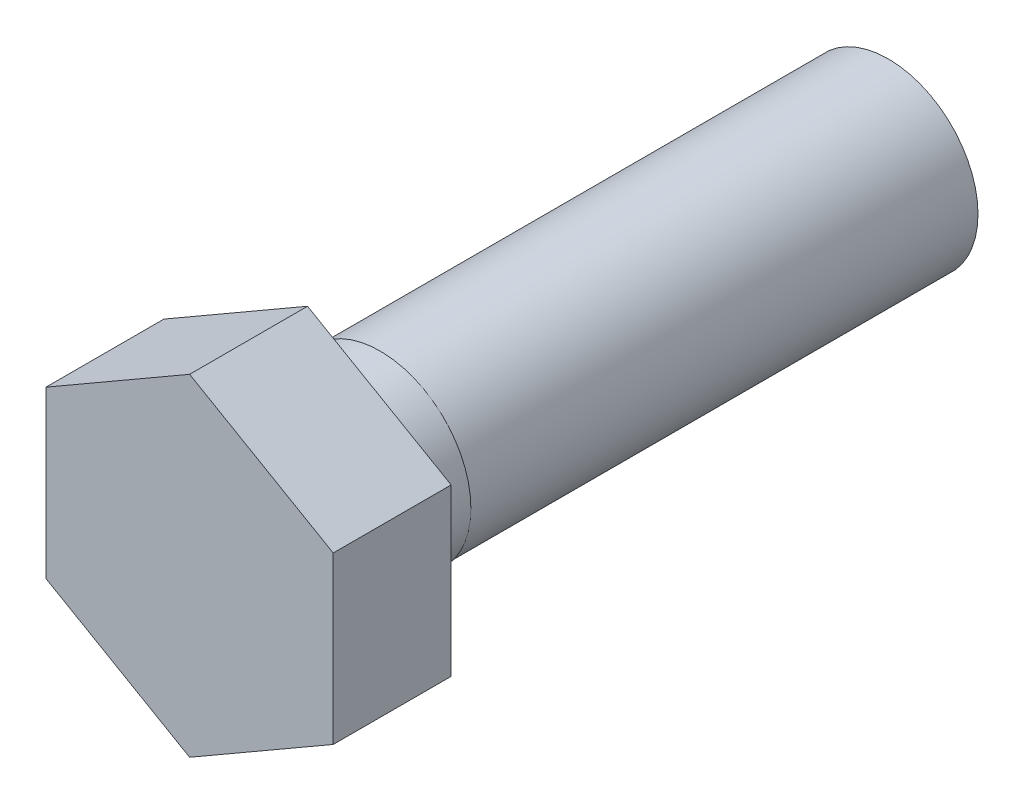
SolidWorks part; units mm, degrees
note: '?' marks a value the reader was unsure of.
ref_plane "Plane1" through (0, 0, 0) normal (0, 0, 1) x (1, 0, 0)
ref_plane "Plane2" through (0, 0, 0) normal (0, 1, 0) x (-1, 0, 0)
ref_plane "Plane3" through (0, 0, 0) normal (1, 0, 0) x (0, 0, -1)
sketch "Head Sketch" plane through (0, 0, 0) normal (0, 0, 1) x (1, 0, 0)
  line L0 (0, 7.2517) -> (6.2801, 3.6258)
  line L1 (6.2801, 3.6258) -> (6.2801, -3.6258)
  line L2 (6.2801, -3.6258) -> (0, -7.2517)
  line L3 (0, -7.2517) -> (-6.2802, -3.6258)
  line L4 (-6.2802, -3.6258) -> (-6.2802, 3.6258)
  line L5 (-6.2802, 3.6258) -> (0, 7.2517)
  line L6 (6.2801, 3.6258) -> (-6.2802, -3.6258) construction
  line L7 (0, 7.2517) -> (0, -7.2517) construction
  line L8 (-6.2802, 3.6258) -> (6.2801, -3.6258) construction
  point P0 (0, 0)
  dimension "D1" = 60
  dimension "D2" = 60
  dimension "Width across flats" = 12.5603
extrude "Head" add sketch "Head Sketch" along normal blind 5.1562
sketch "Shank Sketch" plane through (0, 0, 0) normal (0, 0, 1) x (1, 0, 0)
  line L0 (50, 0) -> (-50, 0) construction
  line L1 (0, -50) -> (0, 50) construction
  circle A0 centre (0, 0) radius 3.9688
  dimension "Shank diameter" = 7.9375
extrude "Shank" add sketch "Shank Sketch" against normal blind 25.4
ref_axis "Axis1" through (0, 0, -75.4) along (0, 0, 1)?
sketch "Thread End" plane through (0, 0, 0) normal (1, 0, 0) x (0, 0, -1)
  line L0 (3.175, 3.9688) -> (3.175, 3.9187)
  line L2 (3.175, 3.9187) -> (25.4, 3.9187)
  line L3 (25.4, 3.9688) -> (3.175, 3.9688)
  line L4 (21.5519, 0) -> (27.4271, 0) construction
  line L5 (25.4, 0) -> (0, 0) construction
  line L6 (25.4, -3.9688) -> (25.4, 3.9688) construction
  line L7 (25.4, 3.9187) -> (25.4, 3.9688)
  line L8 (25.4, 3.9688) -> (0, 3.9688) construction
  dimension "D1" = 0.05
  dimension "Length of thread" = 22.225
revolve "Thread Cut" cut sketch "Thread End" angle 360 about L4
cosmetic thread "Cosmetic Thread2" parameters "D2"=11
